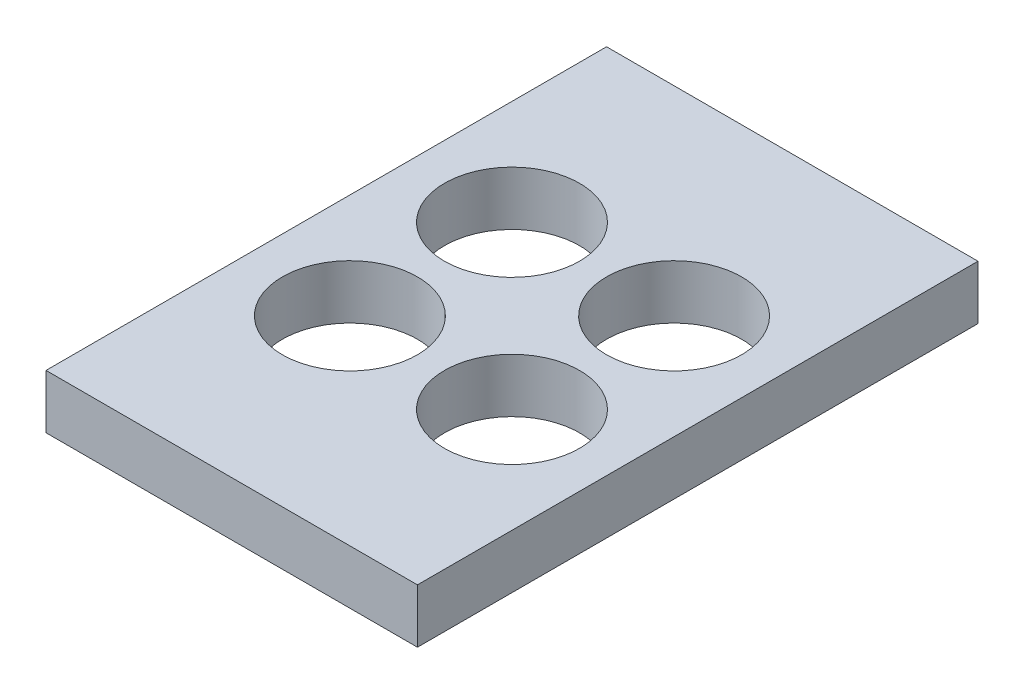
SolidWorks part; units mm, degrees
ref_plane "Front Plane" through (0, 0, 0) normal (0, 0, 1) x (1, 0, 0)
ref_plane "Top Plane" through (0, 0, 0) normal (0, 1, 0) x (1, 0, 0)
ref_plane "Right Plane" through (0, 0, 0) normal (1, 0, 0) x (0, 0, -1)
sketch "Sketch1" plane through (0, 0, 0) normal (0, 1, 0) x (1, 0, 0)
  line L1 (-6.875, -10.375) -> (6.875, -10.375)
  line L2 (-6.875, -10.375) -> (-6.875, 10.375)
  line L3 (-6.875, 10.375) -> (6.875, 10.375)
  line L4 (6.875, -10.375) -> (6.875, 10.375)
  line L5 (-6.875, -10.375) -> (6.875, 10.375) construction
  line L6 (-6.875, 10.375) -> (6.875, -10.375) construction
  point P0 (0, 0)
  dimension "D1" = 13.75
  dimension "D2" = 20.75
extrude "Boss-Extrude1" add sketch "Sketch1" along normal blind 2
sketch "Sketch2" plane through (0, 2, 0) normal (0, 1, 0) x (1, 0, 0)
  line L1 (3, -3) -> (-3, -3) construction
  line L2 (3, -3) -> (3, 3) construction
  line L3 (3, 3) -> (-3, 3) construction
  line L4 (-3, -3) -> (-3, 3) construction
  line L5 (3, -3) -> (-3, 3) construction
  line L6 (3, 3) -> (-3, -3) construction
  circle A0 centre (-3, 3) radius 2.5
  circle A1 centre (3, 3) radius 2.5
  circle A2 centre (3, -3) radius 2.5
  circle A3 centre (-3, -3) radius 2.5
  point P0 (0, 0)
  point P10 (3.0424, 3.0424)
  dimension "D1" = 5
  dimension "D2" = 6
extrude "Cut-Extrude1" cut sketch "Sketch2" against normal through all
